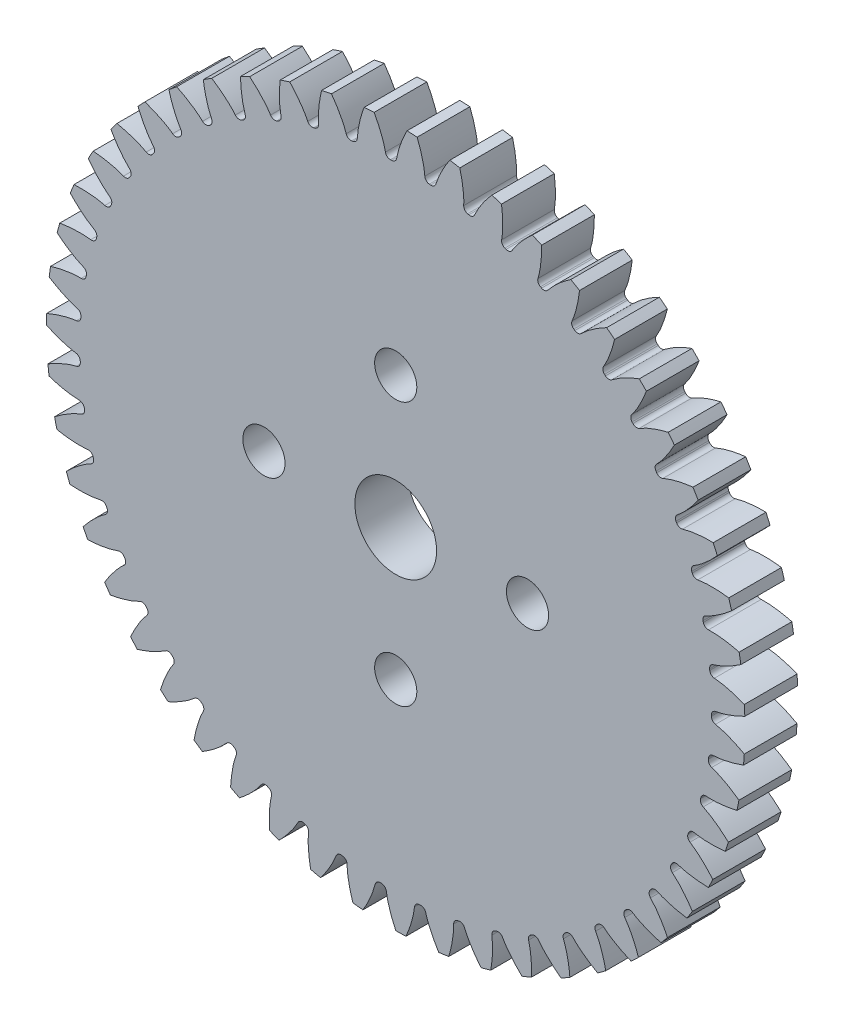
SolidWorks part; units mm, degrees
ref_plane "前基準面" through (0, 0, 0) normal (0, 0, 1) x (1, 0, 0)
ref_plane "上基準面" through (0, 0, 0) normal (0, 1, 0) x (1, 0, 0)
ref_plane "右基準面" through (0, 0, 0) normal (1, 0, 0) x (0, 0, -1)
sketch "草圖2" plane through (0, 0, 0) normal (0, 0, 1) x (1, 0, 0)
  spline S0 degree 4 poles (23.9622, 0) (23.9731, 0.0002) (24.0037, 0.0013) (24.0616, 0.0055) (24.1558, 0.0156) (24.2754, 0.033) (24.4295, 0.0609) (24.6101, 0.1005) (24.8075, 0.151) (25.0208, 0.2136) (25.2322, 0.2828) (25.4418, 0.3579) (25.6491, 0.4383) (25.8985, 0.5422) (26.195, 0.6758) (26.5376, 0.8449) (26.921, 1.0519) (27.3058, 1.279) (27.6795, 1.5155) (28.0507, 1.7693) (28.4054, 2.0252) (28.7667, 2.3059) (29.0968, 2.5726) (29.4582, 2.8873) (29.7475, 3.146) (30.1198, 3.5039) (30.3369, 3.7203) (30.5876, 3.9791) (30.6971, 4.097) (30.7646, 4.1695) knots 0 0 0 0 0 0.005377 0.015084 0.028532 0.04661 0.064855 0.092111 0.119476 0.146842 0.174209 0.201575 0.228941 0.256307 0.307035 0.361767 0.4165 0.471232 0.525964 0.580697 0.635429 0.690161 0.744894 0.799626 0.854358 0.909091 0.954545 1 1 1 1 1 construction
  spline S1 degree 4 poles (23.9622, 0) (23.9731, 0.0002) (24.0037, 0.0013) (24.0616, 0.0055) (24.1558, 0.0156) (24.2754, 0.033) (24.4295, 0.0609) (24.6101, 0.1005) (24.8075, 0.151) (25.0208, 0.2136) (25.2322, 0.2828) (25.4418, 0.3579) (25.6491, 0.4383) (25.8985, 0.5422) (26.195, 0.6758) (26.5376, 0.8449) (26.921, 1.0519) (27.3058, 1.279) (27.6795, 1.5155) (28.0507, 1.7693) (28.4054, 2.0252) (28.7667, 2.3059) (29.0968, 2.5726) (29.4582, 2.8873) (29.7475, 3.146) (30.0391, 3.4263) (30.1799, 3.5647) (30.2514, 3.6362) knots 0 0 0 0 0 0.005377 0.015084 0.028532 0.04661 0.064855 0.092111 0.119476 0.146842 0.174209 0.201575 0.228941 0.256307 0.307035 0.361767 0.4165 0.471232 0.525964 0.580697 0.635429 0.690161 0.744894 0.799626 0.854358 0.909091 0.909091 0.909091 0.909091 0.909091
sketch "草圖3" plane through (0, 0, 0) normal (0, 0, 1) x (1, 0, 0)
  line L0 (0, 0) -> (35.1717, 0) construction
  line L1 (23.9622, 0) -> (23.96, 0)
  line L2 (0, 0) -> (25.4967, -0.4099) construction
  line L3 (23.9498, -0.7703) -> (23.9476, -0.7702)
  circle A0 centre (0, 0) radius 23.96
  circle A1 centre (0, 0) radius 24.25
  circle A2 centre (0, 0) radius 26.5
  arc A3 (25.4967, -0.4099) -> (25.4972, 0.38) centre (0, 0) ccw
  spline S0 degree 4 poles (-27.0773, 3999.1706) (20.1082, 47.2435) (21.4518, 0.6933) (22.8326, -0.1259) (24.1558, 0.0156) (24.2754, 0.033) (24.4295, 0.0609) (24.6101, 0.1005) (24.8075, 0.151) (25.0208, 0.2136) (25.2322, 0.2828) (25.4418, 0.3579) (25.6491, 0.4383) (25.8985, 0.5422) (26.195, 0.6758) (26.5376, 0.8449) (26.921, 1.0519) (27.3058, 1.279) (27.6795, 1.5155) (28.0507, 1.7693) (28.4054, 2.0252) (28.7667, 2.3059) (29.0968, 2.5726) (29.4582, 2.8873) (31.0293, 4.2921) (36.0872, 9.7491) (-39.0216, -64.629) (2857.312, 2832.7589) knots -0.608068 -0.608068 -0.608068 -0.608068 -0.608068 0.005377 0.015084 0.028532 0.04661 0.064855 0.092111 0.119476 0.146842 0.174209 0.201575 0.228941 0.256307 0.307035 0.361767 0.4165 0.471232 0.525964 0.580697 0.635429 0.690161 0.744894 0.799626 0.854358 1.879023 1.879023 1.879023 1.879023 1.879023 only from (23.9622, 0) to (30.2514, 3.6362) construction
  spline S1 degree 4 poles (23.9622, 0) (23.9731, 0.0002) (24.0037, 0.0013) (24.0616, 0.0055) (24.1558, 0.0156) (24.2754, 0.033) (24.4295, 0.0609) (24.6101, 0.1005) (24.8075, 0.151) (25.0208, 0.2136) (25.2322, 0.2828) (25.4418, 0.3579) (25.6491, 0.4383) (25.8985, 0.5422) (26.195, 0.6758) (26.5376, 0.8449) (26.921, 1.0519) (27.3058, 1.279) (27.6795, 1.5155) (28.0507, 1.7693) (28.4054, 2.0252) (28.7667, 2.3059) (29.0968, 2.5726) (29.4582, 2.8873) (29.7475, 3.146) (30.0391, 3.4263) (30.1799, 3.5647) (30.2514, 3.6362) knots 0 0 0 0 0 0.005377 0.015084 0.028532 0.04661 0.064855 0.092111 0.119476 0.146842 0.174209 0.201575 0.228941 0.256307 0.307035 0.361767 0.4165 0.471232 0.525964 0.580697 0.635429 0.690161 0.744894 0.799626 0.854358 0.909091 0.909091 0.909091 0.909091 0.909091
  spline S2 degree 4 poles (23.9498, -0.7703) (23.9607, -0.7708) (23.9913, -0.7729) (24.049, -0.779) (24.1428, -0.7921) (24.2618, -0.8134) (24.4149, -0.8462) (24.5942, -0.8915) (24.7898, -0.9484) (25.001, -1.0179) (25.2101, -1.0937) (25.4171, -1.1756) (25.6218, -1.2626) (25.8677, -1.3744) (26.1598, -1.5175) (26.4967, -1.6975) (26.8733, -1.9168) (27.2506, -2.1561) (27.6165, -2.4045) (27.9793, -2.6701) (28.3256, -2.9373) (28.6777, -3.2295) (28.999, -3.5066) (29.3502, -3.8328) (29.631, -4.1006) (29.9134, -4.3902) (30.0497, -4.533) (30.1189, -4.6068) knots 0 0 0 0 0 0.005377 0.015084 0.028532 0.04661 0.064855 0.092111 0.119476 0.146842 0.174209 0.201575 0.228941 0.256307 0.307035 0.361767 0.4165 0.471232 0.525964 0.580697 0.635429 0.690161 0.744894 0.799626 0.854358 0.909091 0.909091 0.909091 0.909091 0.909091
  dimension "D1" = 51
  dimension "D2" = 53
  dimension "D3" = 48.5
  dimension "D4" = 47.92
  dimension "D5" = 0.79
extrude "填料-伸長1" add sketch "草圖3" along normal blind 4 contours A2
sketch "草圖4" plane through (0, 0, 4) normal (0, 0, 1) x (1, 0, 0)
  line L0 (23.9498, -0.7703) -> (23.9476, -0.7702) construction
  line L1 (23.9622, 0) -> (23.96, 0) construction
  line L2 (23.9498, -0.7703) -> (23.9476, -0.7702)
  line L3 (23.9622, 0) -> (23.96, 0)
  circle A0 centre (0, 0) radius 26.5 construction
  circle A1 centre (0, 0) radius 23.96 construction
  arc A2 (26.4471, -1.6738) -> (26.4872, 0.8228) centre (0, 0) ccw
  arc A3 (23.9476, -0.7702) -> (23.96, 0) centre (0, 0) ccw
  spline S0 degree 4 poles (-67.3716, -1998.6234) (19.8243, -29.0316) (21.8518, -1.1652) (23.0237, -0.6359) (24.1428, -0.7921) (24.2618, -0.8134) (24.4149, -0.8462) (24.5942, -0.8915) (24.7898, -0.9484) (25.001, -1.0179) (25.2101, -1.0937) (25.4171, -1.1756) (25.6218, -1.2626) (25.8677, -1.3744) (26.1598, -1.5175) (26.4967, -1.6975) (26.8733, -1.9168) (27.2506, -2.1561) (27.6165, -2.4045) (27.9793, -2.6701) (28.3256, -2.9373) (28.6777, -3.2295) (28.999, -3.5066) (29.3502, -3.8328) (30.6711, -5.0927) (34.453, -9.411) (-9.5603, 36.9776) (1397.3138, -1464.1787) knots -0.509305 -0.509305 -0.509305 -0.509305 -0.509305 0.005377 0.015084 0.028532 0.04661 0.064855 0.092111 0.119476 0.146842 0.174209 0.201575 0.228941 0.256307 0.307035 0.361767 0.4165 0.471232 0.525964 0.580697 0.635429 0.690161 0.744894 0.799626 0.854358 1.719869 1.719869 1.719869 1.719869 1.719869 only from (23.9498, -0.7703) to (30.1189, -4.6068) construction
  spline S1 degree 4 poles (-3.0882, 1999.7562) (20.7473, 28.3793) (21.878, 0.4621) (23.0322, -0.1046) (24.1558, 0.0156) (24.2754, 0.033) (24.4295, 0.0609) (24.6101, 0.1005) (24.8075, 0.151) (25.0208, 0.2136) (25.2322, 0.2828) (25.4418, 0.3579) (25.6491, 0.4383) (25.8985, 0.5422) (26.195, 0.6758) (26.5376, 0.8449) (26.921, 1.0519) (27.3058, 1.279) (27.6795, 1.5155) (28.0507, 1.7693) (28.4054, 2.0252) (28.7667, 2.3059) (29.0968, 2.5726) (29.4582, 2.8873) (30.819, 4.1041) (34.7377, 8.2986) (-10.744, -36.6512) (1443.6598, 1418.5033) knots -0.509305 -0.509305 -0.509305 -0.509305 -0.509305 0.005377 0.015084 0.028532 0.04661 0.064855 0.092111 0.119476 0.146842 0.174209 0.201575 0.228941 0.256307 0.307035 0.361767 0.4165 0.471232 0.525964 0.580697 0.635429 0.690161 0.744894 0.799626 0.854358 1.719869 1.719869 1.719869 1.719869 1.719869 only from (23.9622, 0) to (30.2514, 3.6362) construction
  spline S2 degree 4 poles (23.9498, -0.7703) (23.9607, -0.7708) (23.9913, -0.7729) (24.049, -0.779) (24.1428, -0.7921) (24.2618, -0.8134) (24.4149, -0.8462) (24.5942, -0.8915) (24.7898, -0.9484) (25.001, -1.0179) (25.2101, -1.0937) (25.4171, -1.1756) (25.6218, -1.2626) (25.8677, -1.3744) (26.0995, -1.488) (26.2794, -1.5821) (26.4085, -1.6525) (26.4471, -1.6738) knots 0 0 0 0 0 0.005377 0.015084 0.028532 0.04661 0.064855 0.092111 0.119476 0.146842 0.174209 0.201575 0.228941 0.256307 0.307035 0.328696 0.328696 0.328696 0.328696 0.328696
  spline S3 degree 4 poles (23.9622, 0) (23.9731, 0.0002) (24.0037, 0.0013) (24.0616, 0.0055) (24.1558, 0.0156) (24.2754, 0.033) (24.4295, 0.0609) (24.6101, 0.1005) (24.8075, 0.151) (25.0208, 0.2136) (25.2322, 0.2828) (25.4418, 0.3579) (25.6491, 0.4383) (25.8985, 0.5422) (26.1338, 0.6482) (26.3166, 0.7365) (26.448, 0.8027) (26.4872, 0.8228) knots 0 0 0 0 0 0.005377 0.015084 0.028532 0.04661 0.064855 0.092111 0.119476 0.146842 0.174209 0.201575 0.228941 0.256307 0.307035 0.328696 0.328696 0.328696 0.328696 0.328696
extrude "除料-伸長1" cut sketch "草圖4" against normal through all
fillet "圓角1" radius 0.38 2 edges at (23.9476, -0.7702, 2) (23.96, 0, 2)
pattern_circular "環狀複製排列1" count 51 over 360 about axis through (0, 0, 4) along (0, 0, 1) of "除料-伸長1", "圓角1"
sketch "草圖5" plane through (0, 0, 4) normal (0, 0, 1) x (1, 0, 0)
  line L0 (0, 0) -> (10, 0) construction
  circle A0 centre (0, 0) radius 3.1
  circle A1 centre (10, 0) radius 1.6
  dimension "D1" = 3.2
  dimension "D2" = 6.2
  dimension "D3" = 10
extrude "除料-伸長2" cut sketch "草圖5" against normal through all
pattern_circular "環狀複製排列2" count 4 over 360 about axis through (0, 0, 4) along (0, 0, 1) of "除料-伸長2"
sketch "草圖6" plane through (0, 0, 4) normal (0, 0, 1) x (1, 0, 0)
  circle A0 centre (0, 0) radius 25.5 construction
  dimension "D1" = 51
equation "\"a\"= 20"
equation "\"M\"= 1"
equation "\"T\"= 51"
equation "\"R\"= 0.38 * \"M\""
equation "\"D\"= \"M\" * \"T\""
equation "\"Da\"= ( \"T\" + 2 ) * \"M\""
equation "\"Df\"= ( \"T\" - 2.5 ) * \"M\""
equation "\"Db\"= \"M\" * \"T\" * cos ( \"a\" )"
equation "\"rb\"= \"Db\" / 2"
equation "\"S\"= pi * \"M\" * 0.5"
